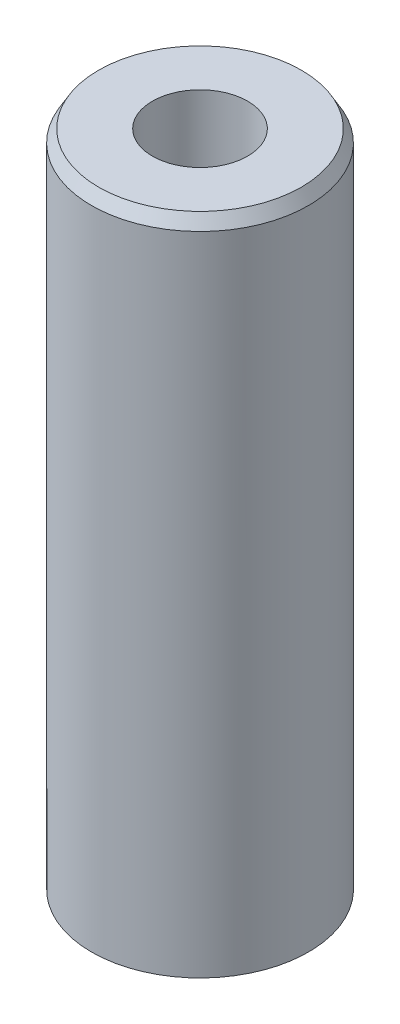
SolidWorks part; units mm, degrees
ref_plane "Front Plane" through (0, 0, 0) normal (0, 0, 1) x (1, 0, 0)
ref_plane "Top Plane" through (0, 0, 0) normal (0, 1, 0) x (1, 0, 0)
ref_plane "Right Plane" through (0, 0, 0) normal (1, 0, 0) x (0, 0, -1)
sketch "Sketch1" plane through (0, 0, 0) normal (0, 1, 0) x (1, 0, 0)
  circle A0 centre (0, 0) radius 47.5
  dimension "SHAFT_OD" = 95
extrude "Boss-Extrude1" add sketch "Sketch1" along normal blind 291.5448
sketch "Sketch2" plane through (0, 0, 0) normal (0, 1, 0) x (1, 0, 0)
  circle A0 centre (0, 0) radius 20.8582
  dimension "BORE_D" = 41.7165
extrude "Cut-Extrude1" cut sketch "Sketch2" along normal through all
chamfer "Chamfer1" distance 5.4103 angle 30 2 edges at (0, 291.5448, 47.5) (0, 0, 47.5) first distance on face at (0, 291.5448, 47.5) first distance on face at (0, 0, 20.8582)
